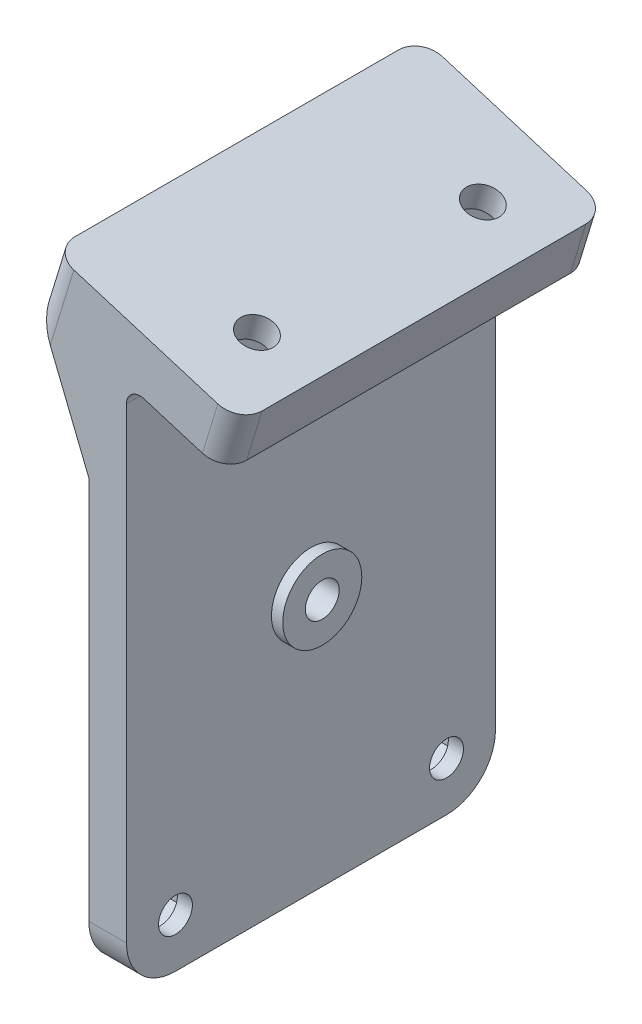
SolidWorks part; units mm, degrees
ref_plane "Plan de face" through (0, 0, 0) normal (0, 0, 1) x (1, 0, 0)
ref_plane "Plan de dessus" through (0, 0, 0) normal (0, 1, 0) x (1, 0, 0)
ref_plane "Plan de droite" through (0, 0, 0) normal (1, 0, 0) x (0, 0, -1)
sketch "Esquisse1" plane through (0, 0, 0) normal (0, 0, 1) x (1, 0, 0)
  line L0 (0, 0) -> (-24.8639, 7.6017)
  line L1 (-24.8639, 7.6017) -> (-26.9105, 0.9075)
  line L2 (-26.9105, 0.9075) -> (-20, -1.2052)
  line L3 (-20, -1.2052) -> (-20, -89.2052)
  line L4 (-20, -89.2052) -> (-15, -89.2052)
  line L5 (-15, -89.2052) -> (-15, -2.7339)
  line L6 (-15, -2.7339) -> (-2.0466, -6.6941)
  line L7 (-2.0466, -6.6941) -> (0, 0)
  line L8 (-24.8639, 7.6017) -> (-0.4628, 7.6017) construction
  dimension "D1" = 7
  dimension "D2" = 26
  dimension "D3" = 17
  dimension "D4" = 15
  dimension "D5" = 5
  dimension "D6" = 88
extrude "Boss.-Extru.1" add sketch "Esquisse1" along normal blind 49
sketch "Esquisse2" plane through (0, 0, 0) normal (0.2924, 0.9563, 0) x (0.9563, -0.2924, 0)
  line L0 (-7.5, 0) -> (-7.5, -49) construction
  line L1 (0, 0) -> (-26, 0) construction
  line L2 (0, -49) -> (-26, -49) construction
  line L3 (0, -49) -> (0, 0) construction
  line L4 (-7.5, -24.5) -> (-17.5689, -24.5) construction
  circle A0 centre (-7.5, -9.5) radius 2.25
  circle A1 centre (-7.5, -39.5) radius 2.25
  dimension "D2" = 4.5
  dimension "D3" = 30
  dimension "D1" = 7.5
extrude "Enlèv. mat.-Extru.1" cut sketch "Esquisse2" against normal up to next and the other way through all
sketch "Esquisse3" plane through (-15, 0, 0) normal (1, 0, 0) x (0, 0, -1)
  line L0 (0, -67.2052) -> (-49, -67.2052) construction
  line L1 (0, -89.2052) -> (0, -2.7339) construction
  line L2 (-49, -89.2052) -> (-49, -2.7339) construction
  line L3 (-49, -89.2052) -> (0, -89.2052) construction
  line L4 (-24.5, -67.2052) -> (-24.5, -39.2052) construction
  circle A0 centre (-42.5, -67.2052) radius 2.25
  circle A1 centre (-6.5, -67.2052) radius 2.25
  circle A2 centre (-24.5, -39.2052) radius 2.25
  dimension "D2" = 4.5
  dimension "D3" = 36
  dimension "D4" = 28
  dimension "D1" = 22
extrude "Enlèv. mat.-Extru.2" cut sketch "Esquisse3" against normal up to next
sketch "Esquisse4" plane through (-15, 0, 0) normal (1, 0, 0) x (0, 0, -1)
  line L0 (-42.5, -67.2052) -> (-49, -67.2052) construction
  line L3 (-24.5, -89.2052) -> (-42.5, -73.7052)
  line L5 (-49, -89.2052) -> (0, -89.2052) construction
  line L6 (-42.5, -73.7052) -> (-42.5, -67.2052) construction
  line L7 (-24.5, -89.2052) -> (-24.5, -37.1138) construction
  line L8 (-6.5, -73.7052) -> (-6.5, -67.2052) construction
  line L9 (-6.5, -67.2052) -> (0, -67.2052) construction
  line L10 (-24.5, -89.2052) -> (-6.5, -73.7052)
  line L11 (-49, -67.2052) -> (-50, -67.2052)
  line L12 (-50, -67.2052) -> (-50, -90.2052)
  line L13 (-50, -90.2052) -> (1, -90.2052)
  line L14 (1, -90.2052) -> (1, -67.2052)
  line L15 (1, -67.2052) -> (0, -67.2052)
  arc A0 (-49, -67.2052) -> (-42.5, -73.7052) centre (-42.5, -67.2052) ccw
  arc A1 (0, -67.2052) -> (-6.5, -73.7052) centre (-6.5, -67.2052) cw
  dimension "D1" = 6.5
  dimension "D2" = 1
  dimension "D3" = 1
extrude "Enlèv. mat.-Extru.3" cut sketch "Esquisse4" against normal up to next (5 mm away)
fillet "Congé1" radius 3 1 edges at (-17.5, -89.2052, 24.5)
sketch "Esquisse5" plane through (0, 0, 0) normal (0.2924, 0.9563, 0) x (0.9563, -0.2924, 0)
  line L0 (0, -24.5) -> (-19.2375, -24.5) construction
  line L1 (-3.95, -11.5496) -> (-3.95, -7.4504)
  line L2 (-3.95, -7.4504) -> (-7.5, -5.4008)
  line L3 (-7.5, -5.4008) -> (-11.05, -7.4504)
  line L4 (-11.05, -7.4504) -> (-11.05, -11.5496)
  line L5 (-11.05, -11.5496) -> (-7.5, -13.5992)
  line L6 (-7.5, -13.5992) -> (-3.95, -11.5496)
  line L7 (0, -49) -> (0, 0) construction
  line L8 (-7.5, -35.4008) -> (-3.95, -37.4504)
  line L9 (-11.05, -37.4504) -> (-7.5, -35.4008)
  line L10 (-11.05, -41.5496) -> (-11.05, -37.4504)
  line L11 (-7.5, -43.5992) -> (-11.05, -41.5496)
  line L12 (-3.95, -41.5496) -> (-7.5, -43.5992)
  line L13 (-3.95, -37.4504) -> (-3.95, -41.5496)
  circle A0 centre (-7.5, -9.5) radius 3.55 construction
  circle A1 centre (-7.5, -39.5) radius 3.55 construction
  dimension "D1" = 7.1
extrude "Enlèv. mat.-Extru.4" cut sketch "Esquisse5" along normal blind 3.5 from vertex starting at point (-2.0466, -6.6941, 0)
sketch "Esquisse6" plane through (0, 0, 49) normal (0, 0, 1) x (1, 0, 0)
  line L0 (-26.9105, 0.9075) -> (-20, -16.2052)
  line L1 (-20, -1.2052) -> (-20, -67.2052) construction
  line L2 (-20, -16.2052) -> (-20, -1.2052)
  line L3 (-20, -1.2052) -> (-26.9105, 0.9075)
  dimension "D1" = 15
extrude "Boss.-Extru.2" add sketch "Esquisse6" against normal up to vertex (49 mm away) up to point (-26.9105, 0.9075, 0)
fillet "Congé2" radius 1.8 1 edges at (-15, -2.7339, 24.5)
fillet "Congé3" radius 3 4 edges at (-25.8872, 4.2546, 0) (-1.0233, -3.3471, 0) (-1.0233, -3.3471, 49) (-25.8872, 4.2546, 49)
sketch "Esquisse8" plane through (-15, 0, 0) normal (1, 0, 0) x (0, 0, -1)
  line L0 (-42.5, -73.7052) -> (-6.5, -73.7052)
  line L1 (-6.5, -73.7052) -> (-6.5, -89.7052)
  line L2 (-6.5, -89.7052) -> (-42.5, -89.7052)
  line L3 (-42.5, -89.7052) -> (-42.5, -73.7052)
  dimension "D1" = 16
extrude "Enlèv. mat.-Extru.5" cut sketch "Esquisse8" against normal through all both and the other way through all
sketch "Esquisse9" plane through (-15, 0, 0) normal (1, 0, 0) x (0, 0, -1)
  circle A0 centre (-24.5, -39.2052) radius 5.25
  circle A1 centre (-24.5, -39.2052) radius 2.25
  circle A3 centre (-24.5, -39.2052) radius 2.25 construction
  dimension "D1" = 3
extrude "Boss.-Extru.3" add sketch "Esquisse9" along normal blind 1.5
sketch "Esquisse10" plane through (-20, 0, 0) normal (-1, 0, 0) x (0, 0, 1)
  line L1 (28.05, -41.2548) -> (28.05, -37.1556)
  line L2 (28.05, -37.1556) -> (24.5, -35.106)
  line L3 (24.5, -35.106) -> (20.95, -37.1556)
  line L4 (20.95, -37.1556) -> (20.95, -41.2548)
  line L5 (20.95, -41.2548) -> (24.5, -43.3044)
  line L6 (24.5, -43.3044) -> (28.05, -41.2548)
  line L7 (10.05, -69.2548) -> (10.05, -65.1556)
  line L8 (10.05, -65.1556) -> (6.5, -63.106)
  line L9 (6.5, -63.106) -> (2.95, -65.1556)
  line L10 (2.95, -65.1556) -> (2.95, -69.2548)
  line L11 (2.95, -69.2548) -> (6.5, -71.3044)
  line L12 (6.5, -71.3044) -> (10.05, -69.2548)
  line L13 (46.05, -69.2548) -> (46.05, -65.1556)
  line L14 (46.05, -65.1556) -> (42.5, -63.106)
  line L15 (42.5, -63.106) -> (38.95, -65.1556)
  line L16 (38.95, -65.1556) -> (38.95, -69.2548)
  line L17 (38.95, -69.2548) -> (42.5, -71.3044)
  line L18 (42.5, -71.3044) -> (46.05, -69.2548)
  circle A0 centre (24.5, -39.2052) radius 3.55 construction
  circle A1 centre (6.5, -67.2052) radius 3.55 construction
  circle A2 centre (42.5, -67.2052) radius 3.55 construction
  dimension "D1" = 7.1
extrude "Enlèv. mat.-Extru.6" cut sketch "Esquisse10" against normal blind 3
fillet "Congé4" [suppressed] radius 3
